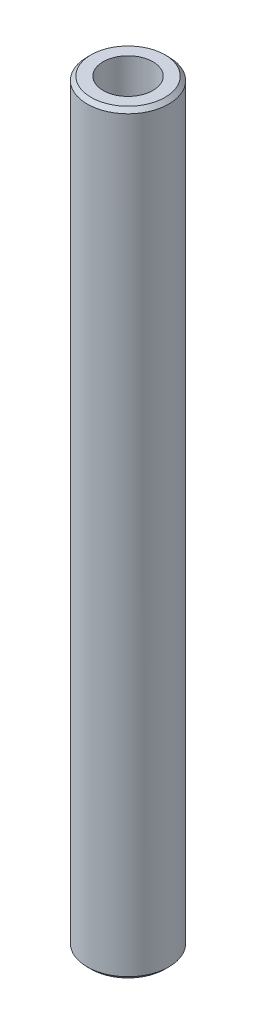
SolidWorks part; units mm, degrees
ref_plane "Front Plane" through (0, 0, 0) normal (0, 0, 1) x (1, 0, 0)
ref_plane "Top Plane" through (0, 0, 0) normal (0, 1, 0) x (1, 0, 0)
ref_plane "Right Plane" through (0, 0, 0) normal (1, 0, 0) x (0, 0, -1)
sketch "Sketch1" plane through (0, 0, 0) normal (0, 1, 0) x (1, 0, 0)
  circle A0 centre (0, 0) radius 22.5
  dimension "SHAFT_OD" = 45
extrude "Boss-Extrude1" add sketch "Sketch1" along normal blind 416.6382
sketch "Sketch2" plane through (0, 0, 0) normal (0, 1, 0) x (1, 0, 0)
  circle A0 centre (0, 0) radius 13.7475
  dimension "BORE_D" = 27.4949
extrude "Cut-Extrude1" cut sketch "Sketch2" along normal through all
chamfer "Chamfer1" distance 2.1221 angle 45 2 edges at (0, 416.6382, 22.5) (0, 0, 22.5)
